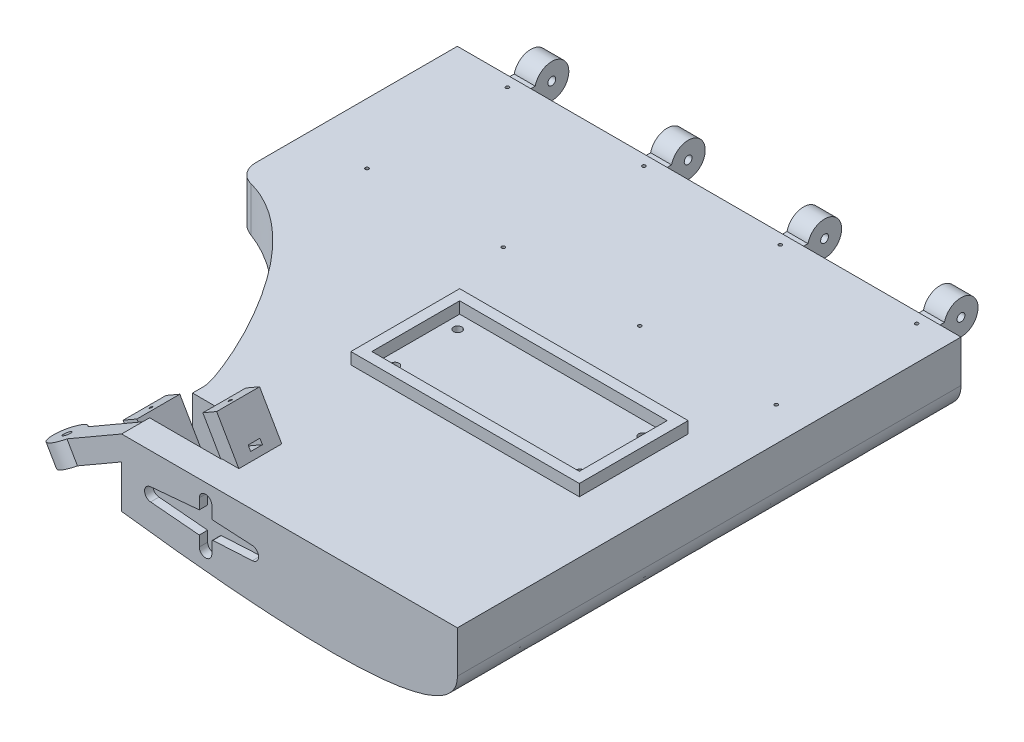
SolidWorks part; units mm, degrees
material "ABS"
ref_plane "Front Plane" through (0, 0, 0) normal (0, 0, 1) x (1, 0, 0)
ref_plane "Top Plane" through (0, 0, 0) normal (0, 1, 0) x (1, 0, 0)
ref_plane "Right Plane" through (0, 0, 0) normal (1, 0, 0) x (0, 0, -1)
sketch "Sketch2" plane through (0, 0, 0) normal (0, 1, 0) x (1, 0, 0)
  line L0 (0, 0) -> (-152.4, 0)
  line L1 (-152.4, 0) -> (-152.4, -152.4)
  line L2 (-152.4, -152.4) -> (0, -152.4)
  line L3 (0, -152.4) -> (0, 0)
  dimension "D1" = 152.4
  dimension "D2" = 152.4
extrude "Boss-Extrude2" add sketch "Sketch2" along normal blind 12.7
ref_plane "Plane2" through (-14.9327, 0, 0) normal (1, 0, 0) x (0, 0, -1)
ref_plane "Plane1" through (-12.7, 0, 0) normal (1, 0, 0) x (0, 0, -1)
sketch "Sketch9" plane through (0, 12.7, 0) normal (0, 1, 0) x (1, 0, 0)
  line L0 (0, 0) -> (0, -48.862) construction
  line L1 (0, -152.4) -> (0, 0) construction
  line L2 (-152.4, 0) -> (-152.4, -48.862) construction
  line L3 (-152.4, 0) -> (-152.4, -152.4) construction
  line L4 (0, 0) -> (-5.4077, 0) construction
  line L5 (0, 0) -> (-152.4, 0) construction
  dimension "D1" = 48.862
  dimension "D2" = 48.862
  dimension "D3" = 5.4077
ref_axis "Axis2" through (-152.4, 12.7, 48.862) along (1, 0, 0)
sketch "Sketch3" plane through (-12.7, 0, 0) normal (1, 0, 0) x (0, 0, -1)
  line L0 (0, 6.35) -> (0, 0)
  line L2 (0, 12.7) -> (0, 0) construction
  line L3 (0, 0) -> (12.7, 0)
  line L4 (12.7, 0) -> (12.7, 6.35)
  line L5 (12.7, 6.35) -> (0, 6.35)
  circle A3 centre (12.7, 5.1562) radius 5.1562
  circle A5 centre (12.7, 5.1562) radius 1.1913
  dimension "D3" = 10.3124
  dimension "D2" = 0
  dimension "D1" = 6.35
extrude "Boss-Extrude3" add sketch "Sketch3" against normal blind 6.35 contours A5 L4 L3 A3 | A5 L4 A3 L3 | A3 L5 L0 L3 region at (-12.7, 2.9629, -4.2993) region at (-12.7, 5.9308, -13.8075) region at (-12.7, 3.4565, -10.2697)
ref_plane "Plane5" through (0, 0, 24.431) normal (0, 0, -1) x (-1, 0, 0)
ref_plane "Plane6" through (0, 12.7, 0) normal (0, 1, 0) x (1, 0, 0)
sketch "Sketch10" plane through (0, 12.7, 0) normal (0, 1, 0) x (1, 0, 0)
  line L0 (0, 0) -> (-152.4, 0) construction
  circle A0 centre (-10.2337, -3.175) radius 0.508
  dimension "D1" = 10.2337
  dimension "D3" = 1.016
  dimension "D2" = 3.175
extrude "Cut-Extrude3" cut sketch "Sketch10" against normal blind 9.525
mirror "Mirror1" about plane through (0, 0, 24.431) normal (0, 0, -1) of "Cut-Extrude3"
fillet "Fillet1" radius 1.5875 3 edges at (-19.05, 3.175, 0) (-15.875, 6.35, 0) (-12.7, 3.175, 0)
pattern_linear "LPattern1" count 4 spacing 41.275 along (-1, 0, 0) of "Boss-Extrude3", "Mirror1", "Fillet1"
sketch "Sketch12" plane through (0, 0, 0) normal (0, 0, -1) x (-1, 0, 0)
  spline S0 degree 1 poles (0, 0) (152.4, 0) knots 0 0 1 1
  spline S1 degree 2 poles (152.4, 0) (-0.2287, -25.399) (0, 0) knots 0 0 0 0.553499 0.553499 0.553499
  spline S2 degree 1 poles (0, 0) (152.4, 0) knots 0 0 1 1
  spline S3 degree 1 poles (152.4, 0) (0, 0) knots 0 0 1 1
  dimension "D1" = 50.8
extrude "Boss-Extrude4" add sketch "Sketch12" against normal up to surface (152.4 mm away) contours S1 | S0 S1 up to face at (-76.2, 6.35, 152.4)
sketch "Sketch13" plane through (0, 12.7, 0) normal (0, 1, 0) x (1, 0, 0)
  line L0 (0, -152.4) -> (0, 0) construction
  line L1 (-81.8426, -69.85) -> (-19.05, -69.85)
  line L2 (-81.8426, -69.85) -> (-81.8426, -96.44)
  line L3 (-81.8426, -96.44) -> (-19.05, -96.44)
  line L4 (-19.05, -69.85) -> (-19.05, -96.44)
  line L5 (0, 0) -> (-152.4, 0) construction
  line L7 (-85.0176, -66.675) -> (-15.875, -66.675)
  line L8 (-85.0176, -66.675) -> (-85.0176, -99.615)
  line L9 (-85.0176, -99.615) -> (-15.875, -99.615)
  line L10 (-15.875, -66.675) -> (-15.875, -99.615)
  dimension "D1" = 62.7926
  dimension "D2" = 26.59
  dimension "D3" = 19.05
  dimension "D4" = 69.85
  dimension "D5" = 3.175
  dimension "D6" = 3.175
  dimension "D7" = 3.175
  dimension "D8" = 3.175
extrude "Boss-Extrude5" add sketch "Sketch13" along normal blind 3.5001
sketch "Sketch14" plane through (0, 12.7, 0) normal (0, 1, 0) x (1, 0, 0)
  line L0 (-19.05, -69.85) -> (-81.8426, -69.85) construction
  line L1 (-81.8426, -69.85) -> (-81.8426, -96.44) construction
  circle A0 centre (-78.1761, -74.1223) radius 1.2497
  circle A1 centre (-22.1767, -74.1223) radius 1.2497
  circle A2 centre (-78.1761, -93.1215) radius 1.2497
  circle A3 centre (-22.1767, -93.1215) radius 1.2497
  dimension "D1" = 4.2723
  dimension "D3" = 3.6665
  dimension "D4" = 55.9994
  dimension "D2" = 18.9992
extrude "Cut-Extrude5" cut sketch "Sketch14" against normal blind 6.35
sketch "Sketch15" plane through (0, 12.7, 0) normal (0, 1, 0) x (1, 0, 0)
  line L0 (-101.6, -152.4) -> (-101.6, -127)
  line L1 (-152.4, -152.4) -> (0, -152.4) construction
  line L2 (-101.6, -127) -> (-152.4, -66.4589)
  line L3 (-152.4, 0) -> (-152.4, -152.4) construction
  line L4 (-152.4, -66.4589) -> (-152.4, -152.4)
  line L5 (-152.4, -152.4) -> (-101.6, -152.4)
  spline S0 degree 3 poles (-101.6, -127) (-102.6273, -119.2728) (-124.8228, -68.0569) (-152.4, -66.4589) knots 0 0 0 0 0.841715 0.841715 0.841715 0.841715
  line M9 (-152.4, 0) -> (-152.4, -152.4)
  line M10 (-152.4, -152.4) -> (0, -152.4)
  dimension "D1" = 50.8
  dimension "D2" = 25.4
  dimension "D3" = 220
extrude "Cut-Extrude6" cut sketch "Sketch15" against normal through all contours L2 S0 | L0 L2 M9 M10 region at (-131.6037, 12.7, 121.8215) region at (-125.8187, 12.7, 91.8783)
sketch "Sketch16" plane through (0, 0, 152.4) normal (0, 0, 1) x (1, 0, 0)
  line L0 (-101.6, 12.7) -> (-101.6, 5.3677)
  line L1 (-101.6, 12.7) -> (-118.0978, 3.175)
  line L2 (-101.6, 5.3677) -> (-118.0978, -4.1573)
  line L3 (-118.0978, 3.175) -> (-118.0978, -4.1573)
  line L4 (-101.6, -7.6022) -> (-101.6, 12.7) construction
  dimension "D1" = 6.35
  dimension "D2" = 60
  dimension "D3" = 19.05
extrude "Boss-Extrude6" add sketch "Sketch16" against normal blind 6.35
sketch "Sketch17" plane through (-27.7243, 48.0198, 0) normal (0.5, -0.866, 0) x (0.866, 0.5, 0)
  line L0 (-104.3544, 146.05) -> (-104.3544, 152.4) construction
  circle A0 centre (-104.3544, 149.225) radius 4.826
  dimension "D1" = 9.652
extrude "Boss-Extrude7" add sketch "Sketch17" against normal up to surface (6.35 mm away) up to face at (-109.8489, 7.9375, 149.225)
sketch "Sketch18" plane through (-27.7243, 48.0198, 0) normal (0.5, -0.866, 0) x (0.866, 0.5, 0)
  circle A0 centre (-104.3544, 149.225) radius 1.143
  dimension "D1" = 2.286
extrude "Cut-Extrude8" cut sketch "Sketch18" against normal up to surface (6.35 mm away) up to face at (-113.8243, 5.6423, 149.225)
ref_plane "Plane7" through (-30.8993, 53.5191, 0) normal (-0.5, 0.866, 0) x (0.866, 0.5, 0)
sketch "Sketch20" plane through (-30.8993, 53.5191, 0) normal (-0.5, 0.866, 0) x (0.866, 0.5, 0)
  line L0 (-86.0567, -130.9381) -> (-86.0567, -143.9239)
  line L1 (-86.0567, -143.9239) -> (-62.911, -143.9239)
  line L2 (-62.911, -143.9239) -> (-62.911, -130.9381)
  line L3 (-62.911, -130.9381) -> (-86.0567, -130.9381)
  dimension "D1" = 12.9857
  dimension "D2" = 23.1457
extrude "Cut-Extrude9" cut sketch "Sketch20" against normal blind 15.494
sketch "Sketch21" plane through (-30.8993, 53.5191, 0) normal (-0.5, 0.866, 0) x (0.866, 0.5, 0)
  line L0 (-86.0373, -130.9653) -> (-90.8633, -130.9653)
  line L1 (-90.8633, -130.9653) -> (-90.8633, -143.951)
  line L2 (-90.8633, -143.951) -> (-86.0373, -143.951)
  line L3 (-86.0373, -143.951) -> (-86.0373, -130.9653)
  line L4 (-63.2251, -143.7536) -> (-58.3991, -143.7536)
  line L5 (-58.3991, -143.7536) -> (-58.3991, -130.7678)
  line L6 (-58.3991, -130.7678) -> (-63.2251, -130.7678)
  line L7 (-63.2251, -130.7678) -> (-63.2251, -143.7536)
  line L8 (6.35, -152.4) -> (6.35, 0) construction
  dimension "D1" = 12.9857
  dimension "D2" = 12.9857
  dimension "D3" = 4.826
  dimension "D4" = 22.8122
  dimension "D5" = 4.826
  dimension "D6" = 64.7491
extrude "Boss-Extrude8" add sketch "Sketch21" against normal up to surface (18.2883 mm away) up to face at (-89.3913, -1.865, 79.9708)
sketch "Sketch22" plane through (-30.8993, 53.5191, 0) normal (-0.5, 0.866, 0) x (0.866, 0.5, 0)
  circle A0 centre (-88.4503, -137.587) radius 0.508
  circle A1 centre (-60.8121, -137.587) radius 0.508
  dimension "D1" = 1.016
  dimension "D2" = 1.016
extrude "Cut-Extrude10" cut sketch "Sketch22" against normal blind 10.16
sketch "Esquisse1" plane through (0, 0, 152.4) normal (0, 0, 1) x (1, 0, 0)
  line L0 (-78.1, 4.563) -> (-78.1, 7.7177)
  line L1 (-74.3, 4.1474) -> (-74.3, 7.7177)
  line L2 (-78.1, 4.563) -> (-92.8263, 3.2599)
  line L3 (-92.8263, -0.7245) -> (-78.1, -2.0277)
  line L4 (-78.1, -2.0277) -> (-78.1, -5.1823)
  line L5 (-74.3, -5.1823) -> (-74.3, -1.612)
  line L6 (-73.9909, -1.3823) -> (-62.0409, -0.7293)
  line L7 (-73.9909, 3.9177) -> (-62.0409, 3.2647)
  arc A0 (-78.1, 7.7177) -> (-74.3, 7.7177) centre (-76.2, 7.7177) cw
  arc A2 (-62.0409, 3.2647) -> (-62.0409, -0.7293) centre (-62.15, 1.2677) cw
  arc A3 (-92.8263, 3.2599) -> (-92.8263, -0.7245) centre (-92.65, 1.2677) ccw
  arc A4 (-78.1, -5.1823) -> (-74.3, -5.1823) centre (-76.2, -5.1823) ccw
  arc A5 (-74.3, 4.1474) -> (-73.9909, 3.9177) centre (-76.2, 1.2677) cw
  arc A6 (-73.9909, -1.3823) -> (-74.3, -1.612) centre (-76.2, 1.2677) cw
extrude "Enlèv. mat.-Extru.2" cut sketch "Esquisse1" against normal blind 2.54
hole_wizard "Dégagement #00001" positions "Esquisse2" profile "Esquisse3" hole size "#0000" standard "Ansi Inch"
sketch "Esquisse2" plane through (0, 0, 149.86) normal (0, 0, 1) x (1, 0, 0)
  point P17 (-76.2, 7.7168)
  point P19 (-61.7499, 1.2677)
  point P21 (-76.2, -5.1814)
  dimension "D3" = 0
  dimension "D4" = 6.4491
  dimension "D5" = 0
  dimension "D6" = 6.4491
  dimension "D7" = 0
  dimension "D8" = 14.4501
sketch "Esquisse3" plane through (-76.2, 7.7168, 149.86) normal (1, 0, 0) x (0, -1, 0)
  line L0 (0, 0) -> (0, 9.652)
  line L1 (0, 9.652) -> (0.5994, 9.652)
  line L2 (0.5994, 9.652) -> (0.5994, 0)
  line L5 (0.5994, 0) -> (0, 0)
  line L10 (0, 9.652) -> (-0.5994, 9.652) construction
  line L11 (0, -6.35) -> (0, 107.95) construction
  dimension "Diamètre du perçage" = 1.1989
  dimension "Profondeur du perçage" = 9.652
  dimension "Angle de pointe" = 180
fillet "Fillet2" radius 6.35 2 edges at (-101.6, 2.5489, 127) (-152.4, 6.35, 66.4589)
sketch "Sketch23" plane through (-50.5751, -29.1996, 0) normal (0.866, 0.5, 0) x (0, 0, -1)
  line L0 (-139.1816, 51.8925) -> (-139.1816, 50.3685)
  line L1 (-139.1816, 50.3685) -> (-135.6256, 50.3685)
  line L2 (-135.6256, 50.3685) -> (-135.6256, 51.8925)
  line L3 (-135.6256, 51.8925) -> (-139.1816, 51.8925)
  line L4 (-143.7536, 61.7985) -> (-130.7678, 61.7985) construction
  line L5 (-143.7536, 48.3814) -> (-143.7536, 61.7985) construction
  dimension "D1" = 9.906
  dimension "D2" = 4.572
  dimension "D3" = 3.556
  dimension "D4" = 1.524
extrude "Cut-Extrude11" cut sketch "Sketch23" against normal up to surface (4.826 mm away) up to face at (-81.2997, 14.365, 135.1532)
